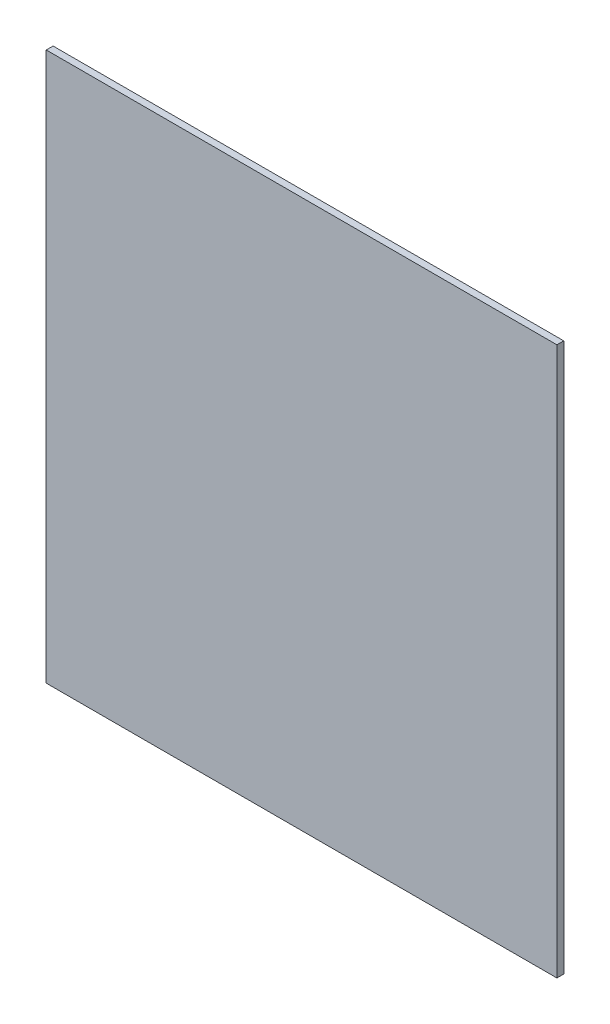
SolidWorks part; units mm, degrees
material "201 Annealed Stainless Steel (SS)"
ref_plane "Front Plane" through (0, 0, 0) normal (0, 0, 1) x (1, 0, 0)
ref_plane "Top Plane" through (0, 0, 0) normal (0, 1, 0) x (1, 0, 0)
ref_plane "Right Plane" through (0, 0, 0) normal (1, 0, 0) x (0, 0, -1)
sketch "Sketch1" plane through (0, 0, 0) normal (0, 0, 1) x (1, 0, 0)
  line L1 (-74.5, -80) -> (74.5, -80)
  line L2 (-74.5, -80) -> (-74.5, 80)
  line L3 (-74.5, 80) -> (74.5, 80)
  line L4 (74.5, -80) -> (74.5, 80)
  line L5 (-74.5, -80) -> (74.5, 80) construction
  line L6 (-74.5, 80) -> (74.5, -80) construction
  point P0 (0, 0)
  dimension "D1" = 149
  dimension "D2" = 160
extrude "Boss-Extrude1" add sketch "Sketch1" along normal blind 2
sketch "Sketch2" plane through (0, 0, 0) normal (0, 0, -1) x (-1, 0, 0)
  line L0 (79, 200) -> (79, -200) construction
  line L1 (-79, 314.7216) -> (-204.3993, 314.7216)
  line L2 (-79, 314.7216) -> (-79, -251.9618)
  line L3 (-79, -251.9618) -> (-204.3993, -251.9618)
  line L4 (-204.3993, 314.7216) -> (-204.3993, -251.9618)
  line L6 (79, 279.3211) -> (244.4765, 279.3211)
  line L7 (79, 279.3211) -> (79, -295.1839)
  line L8 (79, -295.1839) -> (244.4765, -295.1839)
  line L9 (244.4765, 279.3211) -> (244.4765, -295.1839)
  line L10 (-79, -200) -> (-79, -140) construction
  dimension "D1" = 158
extrude "Cut-Extrude1" [suppressed] cut sketch "Sketch2" against normal through all
sketch "Sketch3" plane through (74.5, 0, 0) normal (1, 0, 0) x (0, 0, -1)
  line L0 (-2, 80) -> (0, 80) construction
  line L1 (-2, 80) -> (-2, -80) construction
  circle A0 centre (-7, 65) radius 2.5
  dimension "D3" = 5
  dimension "D1" = 15
  dimension "D2" = 5
surface "Surface-Extrude1" sketch "Sketch3"
sketch "Sketch4" plane through (-74.5, 0, 0) normal (-1, 0, 0) x (0, 0, 1)
  line L1 (2, 80) -> (0, 80) construction
  line L2 (0, -80) -> (0, 80) construction
  point P0 (7.5, 76)
  dimension "D1" = 4
  dimension "D2" = 7.5
ref_axis "Axis1" through (-74.5, 76, 7.5) along (1, 0, 0)
sketch "Sketch5" [suppressed] plane through (0, 0, 0) normal (0, 0, -1) x (-1, 0, 0)
  line L0 (49, 80) -> (49, -80) construction
  line L1 (-49, 80) -> (49, 80)
  line L2 (-49, 80) -> (-49, 60.2594)
  line L3 (-49, 60.2594) -> (49, 60.2594)
  line L4 (49, 80) -> (49, 60.2594)
extrude "Cut-Extrude2" [suppressed] cut sketch "Sketch5" against normal blind 3
sketch "Sketch6" [suppressed] plane through (0, 0, 2) normal (0, 0, 1) x (1, 0, 0)
  line L0 (0, 0) -> (103.2002, 0) construction
  line L1 (-40, 80) -> (-40, 108.3319) construction
  line L2 (-40, 80) -> (-27.987, 80) construction
  line L3 (0, 0) -> (0, 138.3235) construction
  line L4 (40, 80) -> (27.987, 80) construction
  line L5 (40, 80) -> (40, 108.3319) construction
  line L6 (40, -80) -> (40, -108.3319) construction
  line L7 (40, -80) -> (27.987, -80) construction
  line L8 (-40, -80) -> (-27.987, -80) construction
  line L9 (-40, -80) -> (-40, -108.3319) construction
  circle A0 centre (-40, 80) radius 4.5
  circle A2 centre (-45.8, 85.8) radius 1.95
  circle A3 centre (-45.8, 74.2) radius 1.95
  circle A4 centre (-34.2, 74.2) radius 1.95
  circle A5 centre (-34.2, 85.8) radius 1.95
  circle A6 centre (34.2, 85.8) radius 1.95
  circle A7 centre (34.2, 74.2) radius 1.95
  circle A8 centre (45.8, 74.2) radius 1.95
  circle A9 centre (45.8, 85.8) radius 1.95
  circle A10 centre (40, 80) radius 4.5
  circle A11 centre (40, -80) radius 4.5
  circle A12 centre (45.8, -85.8) radius 1.95
  circle A13 centre (45.8, -74.2) radius 1.95
  circle A14 centre (34.2, -74.2) radius 1.95
  circle A15 centre (34.2, -85.8) radius 1.95
  circle A16 centre (-34.2, -85.8) radius 1.95
  circle A17 centre (-34.2, -74.2) radius 1.95
  circle A18 centre (-45.8, -74.2) radius 1.95
  circle A19 centre (-45.8, -85.8) radius 1.95
  circle A20 centre (-40, -80) radius 4.5
  circle A21 centre (-40, 80) radius 5.1 construction
  dimension "D1" = 9
  dimension "D3" = 3.9
extrude "Leandut_holes" [suppressed] cut sketch "Sketch6" against normal through all
chamfer "Chamfer1" [suppressed] distance 5 angle 45
sketch "Sketch7" plane through (0, 0, 2) normal (0, 0, 1) x (1, 0, 0)
  line L0 (74.5, 80) -> (-74.5, 80) construction
  line L1 (-24.5, -125) -> (24.5, -125)
  line L2 (-24.5, -125) -> (-24.5, 60)
  line L3 (-24.5, 60) -> (24.5, 60)
  line L4 (24.5, -125) -> (24.5, 60)
  line L5 (0, 0) -> (0, -66.8576) construction
  line L7 (-74.5, 80) -> (-74.5, -80) construction
  point P0 (0, 0)
  dimension "D1" = 20
  dimension "D2" = 50
  dimension "D3" = 49
  dimension "D4" = 125
extrude "Plunger-Window" [suppressed] cut sketch "Sketch7" against normal through all
sketch "Sketch8" [suppressed] plane through (0, 0, 2) normal (0, 0, 1) x (1, 0, 0)
  line L0 (106, 145) -> (56, 145) construction
  line L1 (-56, 125) -> (56, 125)
  line L2 (-56, 125) -> (-56, 145)
  line L3 (-56, 145) -> (56, 145)
  line L4 (56, 125) -> (56, 145)
  line L5 (56, -110) -> (56, 125) construction
extrude "Cut-Extrude3" [suppressed] cut sketch "Sketch8" against normal blind 5
sketch "Sketch9" [suppressed] plane through (0, 0, 0) normal (0, 0, -1) x (-1, 0, 0)
  line L0 (1.1, 0) -> (-1.1, 0) construction
  line L5 (6, -100) -> (-6, -100)
  line L6 (6, -100) -> (6, 100)
  line L7 (6, 100) -> (-6, 100)
  line L8 (-6, -100) -> (-6, 100)
  line L9 (-81, 120) -> (81, 120) construction
  point P0 (0, 0)
  point P8 (0, 100)
  dimension "D1" = 12
  dimension "D2" = 100
  dimension "D3" = 100
  dimension "D4" = 20
extrude "Plunger-cutout" [suppressed] cut sketch "Sketch9" against normal through all and the other way through all
sketch "Sketch10" plane through (0, 0, 0) normal (0, 0, -1) x (-1, 0, 0)
  line L0 (74.5, -187.5) -> (203.4137, -18.1084) construction
  line L1 (74.5, 80) -> (74.5, -80) construction
  line L2 (74.5, 80) -> (203.4137, -18.1084) construction
  line L3 (74.5, 80) -> (74.5, -187.5) construction
  line L4 (-74.5, 80) -> (74.5, 80) construction
  line L5 (-74.5, 80) -> (74.5, 80) construction
  line L6 (0, 80) -> (0, 262.0874) construction
  line L7 (-74.5, 80) -> (-74.5, -187.5)
  line L8 (-74.5, 80) -> (-203.4137, -18.1084)
  line L9 (-74.5, -187.5) -> (-203.4137, -18.1084)
  line L10 (74.5, 80) -> (74.5, -80) construction
  dimension "D1" = 187.5
  dimension "D2" = 162
  dimension "D3" = 149
  dimension "D4" = 212.8667
  dimension "D5" = 160
extrude "Boss-Extrude3" [suppressed] add sketch "Sketch10" against normal through all
sketch "Sketch11" [suppressed] plane through (0, 0, 2) normal (0, 0, 1) x (1, 0, 0)
  line L0 (81, 217.5) -> (81, -274.1687)
split line "Split Line1" [suppressed]
sketch "Sketch12" [suppressed] plane through (0, 0, 0) normal (0, 0, -1) x (-1, 0, 0)
  line L0 (81, 120) -> (81, -120) construction
  line L4 (106.722, 31) -> (106.722, -31)
  line L5 (174.722, 31) -> (106.722, 31)
  line L6 (174.722, -31) -> (174.722, 31)
  line L7 (106.722, -31) -> (174.722, -31)
  line L8 (81, 31) -> (81, -31)
  line L9 (174.722, 31) -> (81, 31)
  line L10 (174.722, -31) -> (174.722, 31)
  line L11 (81, -31) -> (174.722, -31)
  circle A0 centre (139.72, 0) radius 8
  circle A4 centre (100.7508, -22.5) radius 5 construction
  circle A5 centre (100.7508, 22.5) radius 5 construction
  circle A6 centre (100.7508, -22.5) radius 5
  circle A7 centre (100.7508, 22.5) radius 5
  dimension "D3" = 16
  dimension "D5" = 139.72
  dimension "D1" = 0
extrude "Boss-Extrude4" [suppressed] add sketch "Sketch12" against normal through all
sketch "Sketch13" plane through (0, 0, 0) normal (0, 0, -1) x (-1, 0, 0)
  line L0 (0, 0) -> (-166.9371, 0) construction
  line L1 (108.207, -100) -> (-114.7867, -100)
  line L2 (108.207, -100) -> (108.207, -177.524)
  line L3 (108.207, -177.524) -> (-114.7867, -177.524)
  line L4 (-114.7867, -100) -> (-114.7867, -177.524)
  line L5 (-103.1423, 100) -> (143.0141, 100)
  line L6 (-103.1423, 100) -> (-103.1423, 181.1211)
  line L7 (-103.1423, 181.1211) -> (143.0141, 181.1211)
  line L8 (143.0141, 100) -> (143.0141, 181.1211)
  dimension "D1" = 200
extrude "Cut-Extrude4" [suppressed] cut sketch "Sketch13" against normal through all
